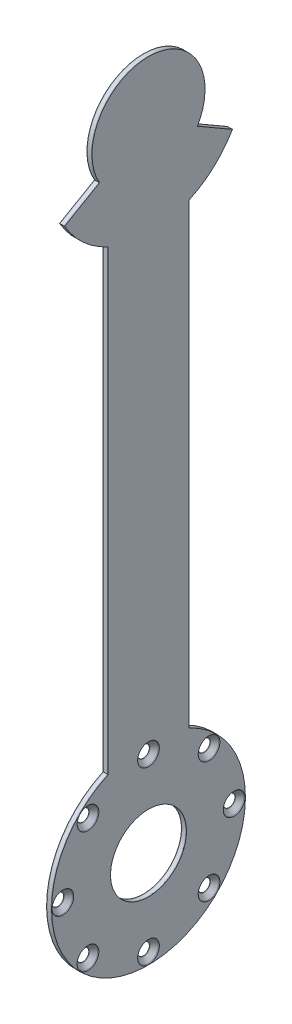
SolidWorks part; units mm, degrees
ref_plane "Front Plane" through (0, 0, 0) normal (0, 0, 1) x (1, 0, 0)
ref_plane "Top Plane" through (0, 0, 0) normal (0, 1, 0) x (1, 0, 0)
ref_plane "Right Plane" through (0, 0, 0) normal (1, 0, 0) x (0, 0, -1)
sketch "Sketch1" plane through (0, 0, 0) normal (1, 0, 0) x (0, 0, -1)
  line L0 (0, 0) -> (0, -392) construction
  line L1 (-30.3109, -17.5) -> (-51.9615, -30)
  line L2 (30.3109, -17.5) -> (51.9615, -30)
  line L5 (-25, -54.5436) -> (-25, -337.4564)
  line L6 (25, -54.5436) -> (25, -337.4564)
  line L7 (0, 0) -> (51.9615, -30) construction
  line L8 (0, 0) -> (-51.9615, -30) construction
  arc A0 (-51.9615, -30) -> (51.9615, -30) centre (0, 0) ccw
  circle A1 centre (0, 0) radius 35
  circle A2 centre (0, -392) radius 60
  circle A3 centre (0, -392) radius 23.5
  point P15 (0, 0)
  dimension "D1" = 120
  dimension "D2" = 70
  dimension "D4" = 47
  dimension "D9" = 120
  dimension "D3" = 392
  dimension "D6" = 60
  dimension "D7" = 60
  dimension "D8" = 50
  dimension "D10" = 282.9129
extrude "Boss-Extrude1" add sketch "Sketch1" against normal blind 0.25 and the other way blind 0.1 contours A1 | A1 L1 A0 L2 | A2 L6 A0 L5 | A2 A3 region at (0, -40.189, 0) region at (0, 0, 0) region at (0, -196, 0) region at (0, -333.6971, 0)
sketch "Sketch2" plane through (-0.25, 0, 0) normal (-1, 0, 0) x (0, 0, 1)
  line L4 (-30.3109, -17.5) -> (-51.9615, -30)
  line L5 (-25, -54.5436) -> (-25, -337.4564)
  line L6 (25, -337.4564) -> (25, -54.5436)
  line L7 (51.9615, -30) -> (30.3109, -17.5)
  line L8 (-30.3109, -17.5) -> (-51.9615, -30)
  line L9 (-25, -54.5436) -> (-25, -337.4564)
  line L10 (25, -337.4564) -> (25, -54.5436)
  line L11 (51.9615, -30) -> (30.3109, -17.5)
  circle A0 centre (0, -392) radius 23.5 construction
  circle A1 centre (0, -392) radius 23.5
  arc A4 (30.3109, -17.5) -> (-30.3109, -17.5) centre (0, 0) ccw
  arc A5 (-51.9615, -30) -> (-25, -54.5436) centre (0, 0) ccw
  arc A6 (-25, -337.4564) -> (25, -337.4564) centre (0, -392) ccw
  arc A7 (25, -54.5436) -> (51.9615, -30) centre (0, 0) ccw
  arc A8 (30.3109, -17.5) -> (-30.3109, -17.5) centre (0, 0) ccw
  arc A9 (-51.9615, -30) -> (-25, -54.5436) centre (0, 0) ccw
  arc A10 (-25, -337.4564) -> (25, -337.4564) centre (0, -392) ccw
  arc A11 (25, -54.5436) -> (51.9615, -30) centre (0, 0) ccw
  arc M9 (30.3109, -17.5) -> (-30.3109, -17.5) centre (0, 0) ccw
  line M10 (-30.3109, -17.5) -> (-51.9615, -30)
  arc M11 (-51.9615, -30) -> (-25, -54.5436) centre (0, 0) ccw
  line M12 (-25, -54.5436) -> (-25, -337.4564)
  arc M13 (-25, -337.4564) -> (25, -337.4564) centre (0, -392) ccw
  line M14 (25, -337.4564) -> (25, -54.5436)
  arc M15 (25, -54.5436) -> (51.9615, -30) centre (0, 0) ccw
  line M16 (51.9615, -30) -> (30.3109, -17.5)
  circle M17 centre (0, -392) radius 23.5
  dimension "D1" = 0
extrude "Boss-Extrude2" add sketch "Sketch2" along normal blind 2.5 separate body contours M16 M9 M10 M11 M12 M13 M14 M15 M17 region at (-0.25, -220.7516, 0)
sketch "Sketch4" plane through (-2.75, 0, 0) normal (-1, 0, 0) x (0, 0, 1)
  line L4 (51.9615, -30) -> (30.3109, -17.5)
  line L5 (-30.3109, -17.5) -> (-51.9615, -30)
  line L6 (-25, -54.5436) -> (-25, -337.4564)
  line L7 (25, -337.4564) -> (25, -54.5436)
  line L8 (51.9615, -30) -> (30.3109, -17.5)
  line L9 (-30.3109, -17.5) -> (-51.9615, -30)
  line L10 (-25, -54.5436) -> (-25, -337.4564)
  line L11 (25, -337.4564) -> (25, -54.5436)
  circle A0 centre (0, -392) radius 23.5 construction
  circle A1 centre (0, -392) radius 23.5
  arc A4 (30.3109, -17.5) -> (-30.3109, -17.5) centre (0, 0) ccw
  arc A5 (-51.9615, -30) -> (-25, -54.5436) centre (0, 0) ccw
  arc A6 (-25, -337.4564) -> (25, -337.4564) centre (0, -392) ccw
  arc A7 (25, -54.5436) -> (51.9615, -30) centre (0, 0) ccw
  arc A8 (30.3109, -17.5) -> (-30.3109, -17.5) centre (0, 0) ccw
  arc A9 (-51.9615, -30) -> (-25, -54.5436) centre (0, 0) ccw
  arc A10 (-25, -337.4564) -> (25, -337.4564) centre (0, -392) ccw
  arc A11 (25, -54.5436) -> (51.9615, -30) centre (0, 0) ccw
  dimension "D1" = 0
extrude "Boss-Extrude3" add sketch "Sketch4" along normal blind 0.25 separate body
sketch "Sketch5" plane through (0.1, 0, 0) normal (1, 0, 0) x (0, 0, -1)
  circle A0 centre (0, -392) radius 53
  point P3 (53, -392)
  point P4 (37.4767, -429.4767)
  point P7 (0, -445)
  point P8 (-37.4767, -429.4767)
  point P9 (-53, -392)
  point P10 (-37.4767, -354.5233)
  point P11 (0, -339)
  point P12 (37.4767, -354.5233)
  dimension "D1" = 106
  dimension "D2" = 8
hole_wizard "CSK for M6 Hex Socket Countersunk Cap Screw1" positions "Sketch5" profile "Sketch6" countersink size "M6" standard "ISO" end condition through all
sketch "Sketch6" plane through (0.1, -354.5233, -37.4767) normal (0, 1, 0) x (0, 0, -1)
  line L0 (0, 0) -> (0, 3.1)
  line L1 (0, 3.1) -> (3.3, 3.1)
  line L2 (3.3, 3.1) -> (3.3, 3.42)
  line L3 (3.3, 3.42) -> (6.72, 0)
  line L5 (6.72, 0) -> (0, 0)
  line L6 (-3.3, 3.42) -> (-6.72, 0) construction
  line L11 (0, -6.35) -> (0, 107.95) construction
  dimension "Thru Hole Dia." = 6.6
  dimension "Thru Hole Depth" = 3.1
  dimension "Near C'Sink Dia." = 13.44
  dimension "Near C'Sink Angle" = 90
sketch "Sketch7" plane through (0.1, 0, 0) normal (1, 0, 0) x (0, 0, -1)
  circle A0 centre (0, 0) radius 17.5
  circle A1 centre (0, 0) radius 12
  point P4 (0, 12)
  point P7 (11.4127, 3.7082)
  point P8 (7.0534, -9.7082)
  point P9 (-7.0534, -9.7082)
  point P10 (-11.4127, 3.7082)
  dimension "D1" = 35
  dimension "D2" = 24
  dimension "D3" = 5
